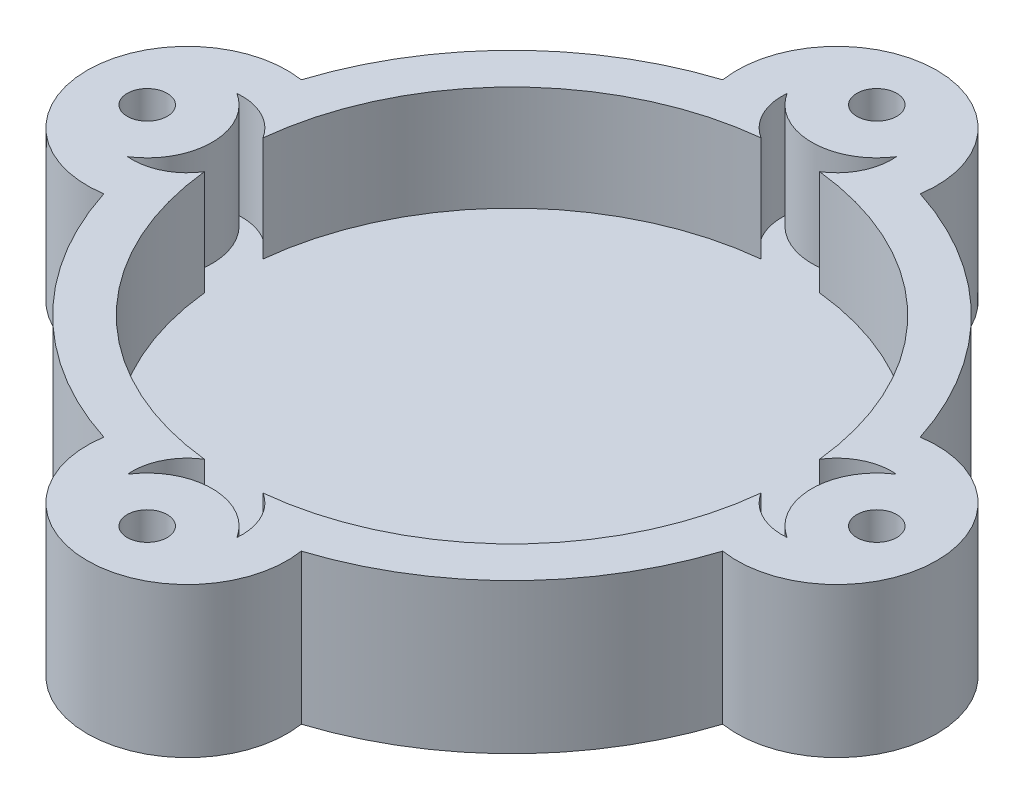
SolidWorks part; units mm, degrees
ref_plane "Front Plane" through (0, 0, 0) normal (0, 0, 1) x (1, 0, 0)
ref_plane "Top Plane" through (0, 0, 0) normal (0, 1, 0) x (1, 0, 0)
ref_plane "Right Plane" through (0, 0, 0) normal (1, 0, 0) x (0, 0, -1)
sketch "Sketch1" plane through (0, 0, 0) normal (0, 1, 0) x (1, 0, 0)
  arc A13 (61.9231, -19.7619) -> (61.9231, 19.7619) centre (65, 0) ccw
  circle A14 centre (0, 0) radius 65
  arc A15 (19.7619, 61.9231) -> (-19.7619, 61.9231) centre (0, 65) ccw
  circle A16 centre (0, 73) radius 4
  circle A17 centre (73, 0) radius 4
  arc A18 (-19.7619, -61.9231) -> (19.7619, -61.9231) centre (0, -65) ccw
  circle A19 centre (0, -73) radius 4
  arc A20 (-61.9231, 19.7619) -> (-61.9231, -19.7619) centre (-65, 0) ccw
  circle A21 centre (-73, 0) radius 4
  point P26 (0, 0)
  point P32 (0, 0)
  dimension "D1" = 130
  dimension "D3" = 8
  dimension "D2" = 40
  dimension "D4" = 8
  dimension "D5" = 4
extrude "Boss-Extrude1" add sketch "Sketch1" along normal blind 30 contours A14 A20 A21 | A14 A18 A19 | A14 | A14 A13 A17 | A14 A15 A16 region at (64.6825, 0, 10.071) region at (0, 0, 0) region at (0, 0, 84.5382) region at (0, 0, -65.4618) region at (-84.5382, 0, 0)
shell "Shell1" thickness 9 removed face at (-73, 30, 4)
